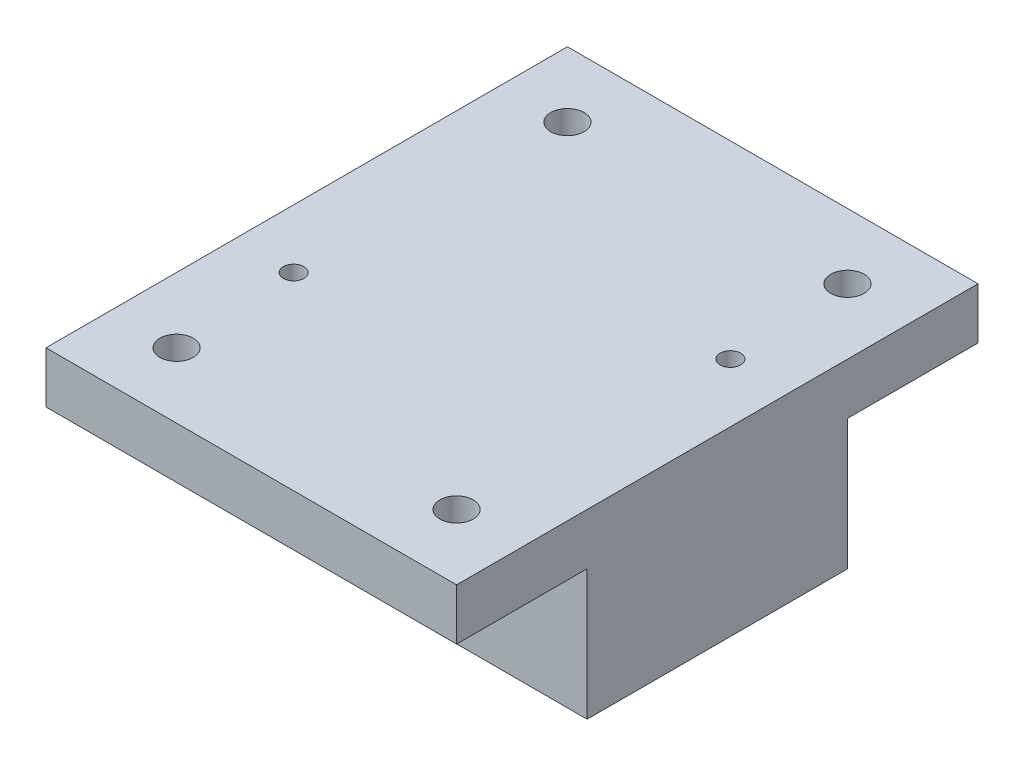
SolidWorks part; units mm, degrees
material "PETG"
ref_plane "Front Plane" through (0, 0, 0) normal (0, 0, 1) x (1, 0, 0)
ref_plane "Top Plane" through (0, 0, 0) normal (0, 1, 0) x (1, 0, 0)
ref_plane "Right Plane" through (0, 0, 0) normal (1, 0, 0) x (0, 0, -1)
sketch "Sketch1" plane through (0, 0, 0) normal (0, 1, 0) x (1, 0, 0)
  line L0 (-27.2813, 38.0813) -> (-27.2813, 50.8) construction
  line L1 (-40, -25.3625) -> (40, -25.3625)
  line L2 (-40, -25.3625) -> (-40, 25.3625)
  line L3 (-40, 25.3625) -> (40, 25.3625)
  line L4 (40, -25.3625) -> (40, 25.3625)
  line L5 (-40, 50.8) -> (40, 50.8)
  line L6 (-40, 50.8) -> (-40, -50.8)
  line L7 (-40, -50.8) -> (40, -50.8)
  line L8 (40, 50.8) -> (40, -50.8)
  line L9 (-27.2813, 38.0813) -> (-40, 38.0813) construction
  line L10 (-27.2813, 38.0813) -> (-27.2813, 25.3625) construction
  line L11 (27.2813, 38.0813) -> (40, 38.0813) construction
  line L13 (-27.2813, -38.0812) -> (-27.2813, -25.3625) construction
  circle A0 centre (-27.2813, 38.0813) radius 3.25
  circle A1 centre (27.2813, 38.0813) radius 3.25
  circle A2 centre (-27.2813, -38.0812) radius 3.25
  circle A3 centre (27.2813, -38.0812) radius 3.25
  point P4 (-40, 0)
  point P5 (0, 25.3625)
  dimension "D4" = 6.5
  dimension "D1" = 50.725
  dimension "D2" = 80
  dimension "D3" = 101.6
extrude "Boss-Extrude1" add sketch "Sketch1" along normal blind 10 contours L1 L4 L3 L2 | L8 L1 L6 L7 | L8 L5 L6 L3 region at (0, 0, 0) region at (0, 0, 38.0812) region at (0, 0, -38.0812)
extrude "Boss-Extrude2" add sketch "Sketch1<3>" against normal blind 25.4 contours L1 L4 L3 L2 region at (0, 0, 0)
sketch "Sketch1<3>" plane through (0, 0, 0) normal (0, 1, 0) x (1, 0, 0) same geometry as "Sketch1"
sketch "Sketch2" plane through (0, 10, 0) normal (0, 1, 0) x (1, 0, 0)
  line L0 (-40, 0) -> (40, 0) construction
  line L1 (-40, -50.8) -> (-40, 50.8) construction
  line L2 (40, -50.8) -> (40, 50.8) construction
  line L3 (0, 50.8) -> (0, -50.8) construction
  line L4 (-40, 50.8) -> (40, 50.8) construction
  line L5 (-40, -50.8) -> (40, -50.8) construction
  line L6 (-28.575, -13.97) -> (-28.575, 0) construction
  line L7 (-28.575, -13.97) -> (0, -13.97) construction
  line L8 (28.575, 0) -> (28.575, 13.97) construction
  line L9 (28.575, 13.97) -> (0, 13.97) construction
  circle A0 centre (-28.575, -13.97) radius 2
  circle A1 centre (28.575, 13.97) radius 2
  dimension "D2" = 4
  dimension "D1" = 13.97
  dimension "D3" = 28.575
extrude "Cut-Extrude1" cut sketch "Sketch2" against normal through all
equation "\"tol_dia_id_intfc\"= 0.0500mm ' For hole diameters - Interference fit"
equation "\"tol_dia_id_slip\"= 0.0750mm ' For hole diameters - Slip fit"
equation "\"tol_dia_id_clear\"= 0.1000mm ' For hole diameters - Clearance fit"
equation "\"tol_dia_od_intfc\"= 0.0500mm ' For shaft diameters - Interference fit"
equation "\"tol_dia_od_slip\"= 0.0750mm ' For shaft diameters - Slip fit"
equation "\"tol_dia_od_clear\"= 0.1000mm ' For shaft diameters - Clearance fit"
equation "\"tol_general_intfc\"= 0.0250mm ' For general parts (Horiz) - Interference fit"
equation "\"tol_general_slip\"= 0.0375mm ' For general parts (Horiz) - Slip fit"
equation "\"tol_general_clear\"= 0.0500mm ' For general parts (Horiz) - Clearance fit"
equation "\"tol_layer_intfc\"= 0.0250mm ' For all parts (Vert) - Interference fit"
equation "\"tol_layer_slip\"= 0.0375mm ' For all parts (Vert) - Slip fit"
equation "\"tol_layer_clear\"= 0.0500mm ' For all parts (Vert) - Clearance fit"
equation "\"tol_corner_rad\"= 0.100mm ' For corners that fit into other parts"
equation "\"D1@Sketch1\"=50.80mm-\"tol_general_slip\"*2"
equation "\"D2@Sketch2\"=3.95+\"tol_dia_id_intfc\""
